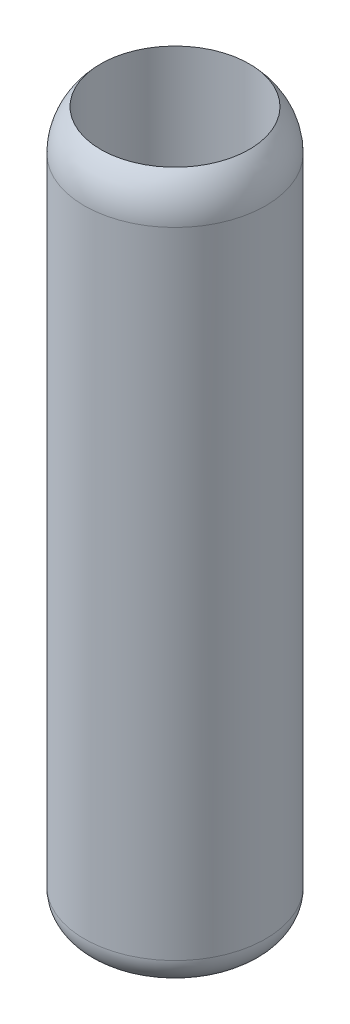
SolidWorks part; units mm, degrees
ref_plane "Front Plane" through (0, 0, 0) normal (0, 0, 1) x (1, 0, 0)
ref_plane "Top Plane" through (0, 0, 0) normal (0, 1, 0) x (1, 0, 0)
ref_plane "Right Plane" through (0, 0, 0) normal (1, 0, 0) x (0, 0, -1)
sketch "Sketch3" plane through (0, 0, 0) normal (0, 1, 0) x (1, 0, 0)
  line L0 (0.8783, 0) -> (0, 0) construction
  circle A0 centre (0, 0) radius 12.7
  circle A1 centre (0, 0) radius 15.5
  dimension "D1" = 25.4
  dimension "D2" = 31
extrude "Boss-Extrude5" add sketch "Sketch3" along normal blind 120
fillet "Fillet5" radius 10 1 edges at (0, 120, 15.5)
fillet "Fillet6" radius 5 1 edges at (0, 0, 15.5)
